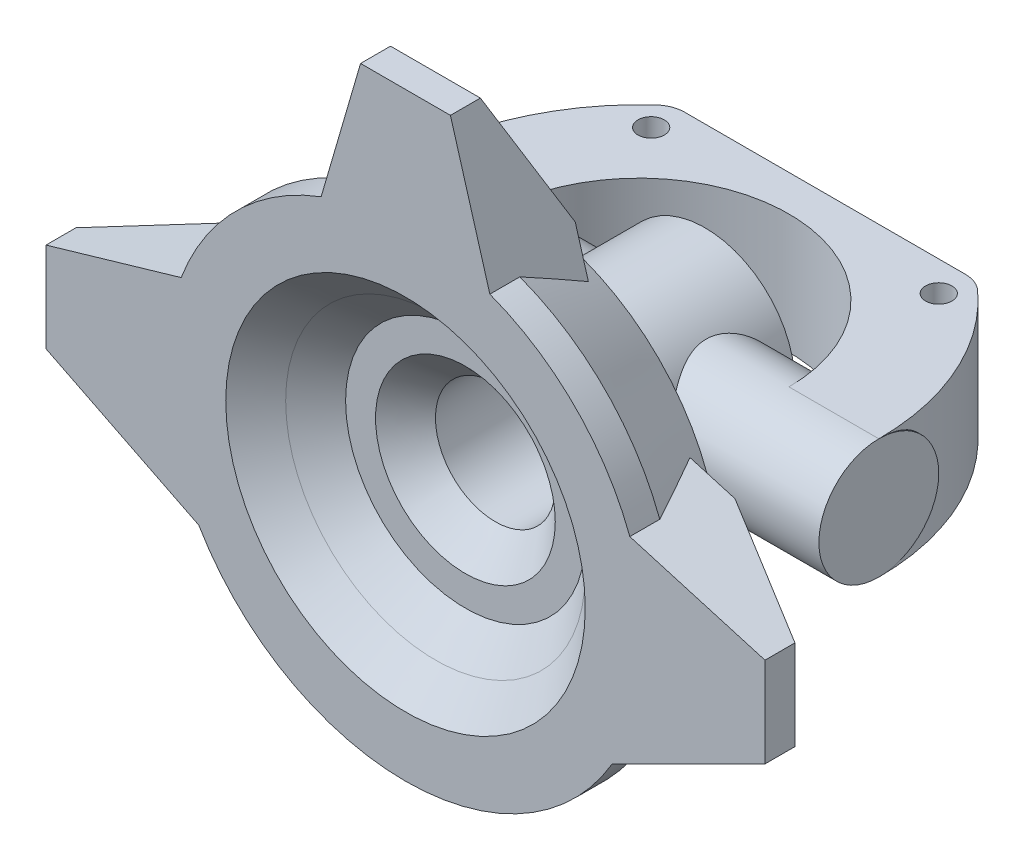
SolidWorks part; units mm, degrees
ref_plane "Front Plane" through (0, 0, 0) normal (0, 0, 1) x (1, 0, 0)
ref_plane "Top Plane" through (0, 0, 0) normal (0, 1, 0) x (1, 0, 0)
ref_plane "Right Plane" through (0, 0, 0) normal (1, 0, 0) x (0, 0, -1)
sketch "Sketch3" plane through (0, 0, 0) normal (1, 0, 0) x (0, 0, -1)
  line L0 (0, 0) -> (59.2999, 0) construction
  line L1 (0, 0) -> (0, 40)
  line L2 (0, 40) -> (5, 40)
  line L3 (5, 40) -> (17.5, 35)
  line L4 (17.5, 35) -> (20, 31)
  line L5 (20, 31) -> (20, 25)
  line L6 (20, 25) -> (30, 15)
  line L7 (30, 15) -> (50, 15)
  line L8 (50, 15) -> (50, 0)
  line L9 (0, 0) -> (50, 0)
  dimension "D1" = 80
  dimension "D2" = 5
  dimension "D3" = 70
  dimension "D4" = 12.5
  dimension "D5" = 2.5
  dimension "D6" = 62
  dimension "D7" = 50
  dimension "D8" = 30
  dimension "D9" = 10
  dimension "D10" = 20
revolve "Revolve1" add sketch "Sketch3" angle 360 about L0
sketch "Sketch4" plane through (0, 0, 0) normal (0, 0, 1) x (1, 0, 0)
  line L0 (-7.5, 60) -> (-14.08, 37.44)
  line L1 (-7.5, 60) -> (7.5, 60)
  line L2 (7.5, 60) -> (14.08, 37.44)
  line L3 (0, 0) -> (0, 67.2644) construction
  line L4 (0, 0) -> (-75.7735, 0) construction
  line L5 (-60, 7.5) -> (-60, -7.5)
  line L6 (-60, -7.5) -> (-34.5039, -20.2357)
  line L7 (-60, 7.5) -> (-37.44, 14.08)
  line L8 (60, 7.5) -> (60, -7.5)
  line L9 (60, -7.5) -> (34.5039, -20.2357)
  line L10 (60, 7.5) -> (37.44, 14.08)
  line L11 (-37.44, 14.08) -> (-15.9666, 20.3431)
  line L12 (-15.9666, 20.3431) -> (-11.5439, -31.7045)
  line L13 (-11.5439, -31.7045) -> (-34.5039, -20.2357)
  line L14 (37.44, 14.08) -> (18.6087, 19.5725)
  line L15 (34.5039, -20.2357) -> (8.9681, -32.9912)
  line L16 (8.9681, -32.9912) -> (18.6087, 19.5725)
  line L17 (-14.08, 37.44) -> (-18.3327, 22.8593)
  line L18 (-18.3327, 22.8593) -> (18.3327, 22.8593)
  line L19 (18.3327, 22.8593) -> (14.08, 37.44)
  circle A0 centre (0, 0) radius 40 construction
  dimension "D6" = 60
  dimension "D1" = 23.5
  dimension "D2" = 15
  dimension "D3" = 60
  dimension "D4" = 23.5
  dimension "D5" = 15
  dimension "D7" = 28.5
extrude "Boss-Extrude1" add sketch "Sketch4" against normal blind 15
sketch "Sketch7" plane through (0, 0, 0) normal (0, 1, 0) x (1, 0, 0)
  line L0 (-40, 49) -> (-40, 39)
  line L1 (0, 0) -> (0, 36.5) construction
  line L2 (-40, 39) -> (40, 39) construction
  line L5 (-40, 49) -> (40, 49)
  line L7 (15, 50) -> (-15, 50) construction
  line L8 (40, 49) -> (40, 39)
  line L9 (24.1466, 39) -> (62.417, 39) construction
  line L10 (-40, 39) -> (40, 39)
  dimension "D1" = 80
  dimension "D2" = 10
  dimension "D3" = 11
revolve "Revolve3" add sketch "Sketch7" angle 360 about L9
sketch "Sketch8" plane through (0, 0, 0) normal (0, 1, 0) x (1, 0, 0)
  line L0 (0, 0) -> (0, 39) construction
  line L1 (-40, 39) -> (0, 39) construction
  line L2 (-40, 49) -> (-40, 29) construction
  line L3 (-40, 39) -> (-25, 39)
  line L4 (25, 39) -> (40, 39)
  arc A0 (40, 39) -> (-40, 39) centre (0, 39) ccw
  arc A1 (25, 39) -> (-25, 39) centre (0, 39) ccw
  point P4 (-25, 39)
  dimension "D1" = 15
extrude "Boss-Extrude2" add sketch "Sketch8" along normal blind 10 and the other way blind 10
sketch "Sketch9" plane through (0, 10, 0) normal (0, 1, 0) x (1, 0, 0)
  line L0 (-24, 65) -> (24, 65) construction
  line L1 (0, 0) -> (0, 99.7114) construction
  line L2 (60, 0) -> (37.44, 0) construction
  circle A0 centre (-24, 65) radius 2.2
  circle A1 centre (24, 65) radius 2.2
  dimension "D1" = 4.4
  dimension "D2" = 48
  dimension "D3" = 65
extrude "Cut-Extrude1" cut sketch "Sketch9" against normal through all
sketch "Sketch10" plane through (0, 10, 0) normal (0, 1, 0) x (1, 0, 0)
  line L1 (44.3943, 70) -> (-51.2906, 70)
  line L2 (44.3943, 70) -> (44.3943, 96.7228)
  line L3 (44.3943, 96.7228) -> (-51.2906, 96.7228)
  line L4 (-51.2906, 70) -> (-51.2906, 96.7228)
  circle A0 centre (-24, 65) radius 2.2 construction
  dimension "D1" = 5
extrude "Cut-Extrude2" cut sketch "Sketch10" against normal through all
fillet "Fillet1" radius 5 2 edges at (25.2784, 0, -70) (-25.2784, 0, -70)
chamfer "Chamfer2" distance 20 distance2 10 3 edges at (60, 0, -15) (-60, 0, -15) (0, 60, -15) first distance on face at (46.3069, -2.3676, -15) first distance on face at (-46.3069, -2.3676, -15) first distance on face at (0, 47.1199, -15)
sketch "Sketch11" plane through (0, 0, 0) normal (0, 0, 1) x (1, 0, 0)
  circle A0 centre (0, 0) radius 25
  arc A1 (-14.08, 37.44) -> (-37.44, 14.08) centre (0, 0) ccw construction
  dimension "D1" = 15
extrude "Cut-Extrude3" cut sketch "Sketch11" against normal offset from surface (10 mm away) 10 up to face at (31, 0, -20)
sketch "Sketch12" plane through (0, 0, -50) normal (0, 0, -1) x (-1, 0, 0)
  circle A0 centre (0, 0) radius 10
  circle A1 centre (0, 0) radius 15 construction
  dimension "D1" = 5
extrude "Cut-Extrude4" cut sketch "Sketch12" against normal through all from offset 3 offset against normal yes
chamfer "Chamfer3" distance 5 angle 45 3 edges at (25, 0, -10) (25, 0, 0) (10, 0, -10)
equation "\"`0\"=7"
